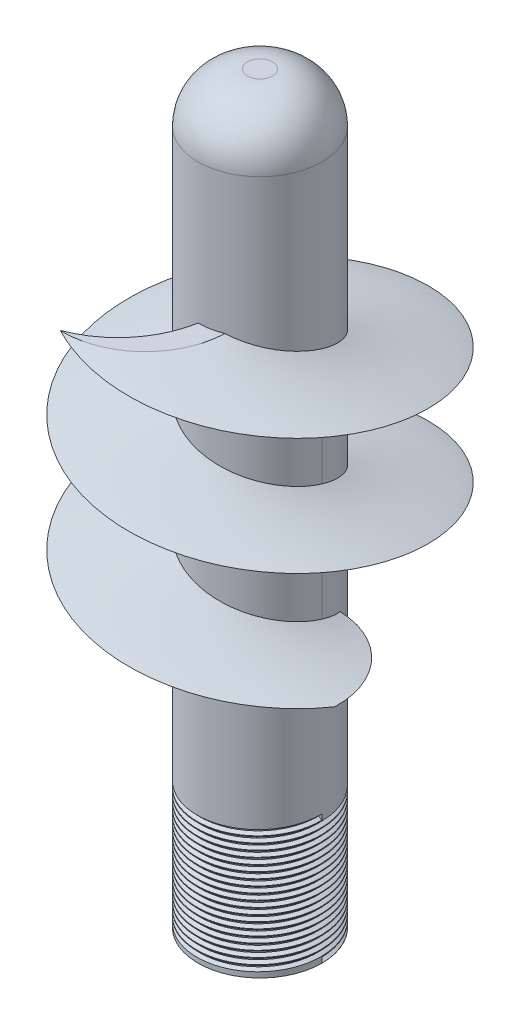
SolidWorks part; units mm, degrees
ref_plane "Front Plane" through (0, 0, 0) normal (0, 0, 1) x (1, 0, 0)
ref_plane "Top Plane" through (0, 0, 0) normal (0, 1, 0) x (1, 0, 0)
ref_plane "Right Plane" through (0, 0, 0) normal (1, 0, 0) x (0, 0, -1)
sketch "Sketch1" plane through (0, 0, 0) normal (0, 1, 0) x (1, 0, 0)
  circle A0 centre (0, 0) radius 3.175
extrude "Boss-Extrude1" add sketch "Sketch1" along normal blind 38.1
fillet "Fillet1" radius 2.54 1 edges at (0, 38.1, 3.175)
thread "Thread1" pitch 0.3175 method cut profile "Thread Profile1" start angle 0, offset 0, length 6.35, pitch 0.3175, diameter 6.35
ref_plane "Plane1" through (3.175, 0, 0) normal (0, 0, 1) x (1, 0, 0)
sketch "Thread Profile1" plane through (3.175, 0, 0) normal (0, 0, 1) x (1, 0, 0)
  line L0 (0, 0) -> (0, 0.3175) construction
  line L11 (0, 0) -> (0, 0.2778)
  line L12 (0, 0.2778) -> (-0.1719, 0.1786)
  line L13 (-0.1719, 0.1786) -> (-0.1719, 0.0992)
  line L15 (-0.1719, 0.0992) -> (0, 0)
  line L17 (-0.1719, 0.1389) -> (0, 0.1389) construction
  point P2 (0, 0)
  dimension "Pitch" = 0.3175
  dimension "Profile_Angle" = 60
  dimension "Profile_Land" = 0.0794
  dimension "Profile_Height" = 0.1719
ref_plane "Plane2" through (0, 14.9133, 0) normal (0, 1, 0) x (1, 0, 0)
sketch "Sketch3" plane through (0, 14.9133, 0) normal (0, 1, 0) x (1, 0, 0)
  circle A0 centre (0, 0) radius 3.175
curve "Helix/Spiral1" pitch 6 height 13.5 radius 3.175 left hand yes centre (0, 14.9133, 0) axis (0, 1, 0) start towards (0, 0, 1)
sketch "Sketch4" [suppressed] plane through (0, 14.9133, 0) normal (0, 1, 0) x (1, 0, 0)
  circle A0 centre (0, 0) radius 3.175
sketch "Sketch11" plane through (0, 14.9133, 0) normal (0, 1, 0) x (1, 0, 0)
  arc A0 (3.175, 0) -> (7.0352, -3.1996) centre (2.2983, -4.9862) cw
  arc A1 (7.0352, -3.1996) -> (2.957, 1.1563) centre (2.8182, -3.0608) ccw
  circle A2 centre (0, 0) radius 3.175 construction
  arc A3 (2.957, 1.1563) -> (3.175, 0) centre (0, 0) cw
sweep "Sweep1" add profiles "Sketch11" path "Helix/Spiral1"
